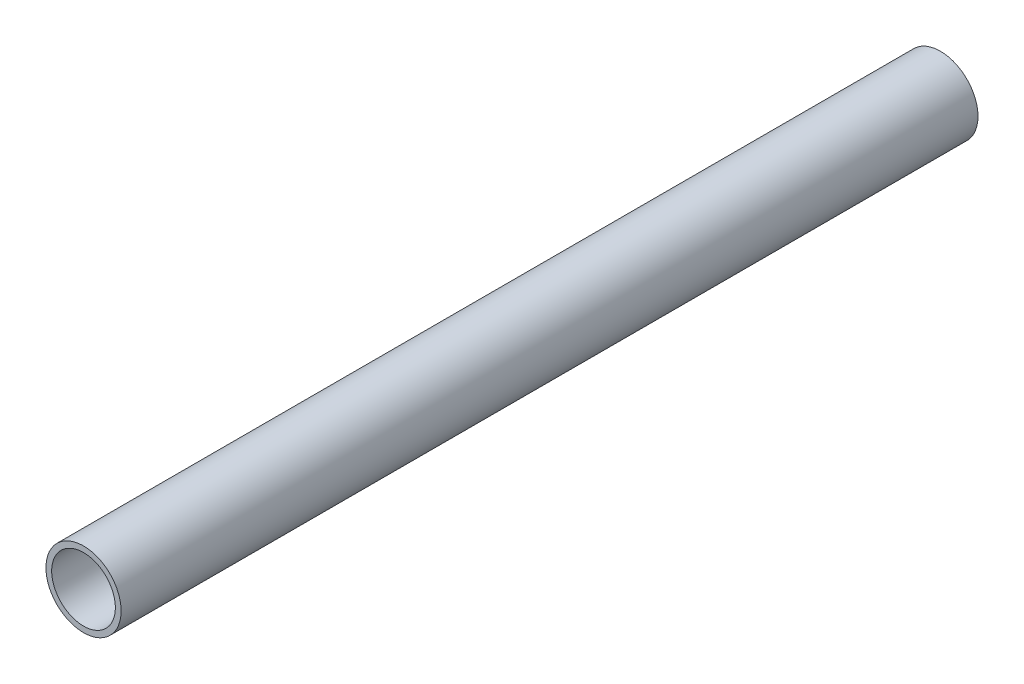
SolidWorks part; units mm, degrees
material "Alloy Steel"
ref_plane "Front Plane" through (0, 0, 0) normal (0, 0, 1) x (1, 0, 0)
ref_plane "Top Plane" through (0, 0, 0) normal (0, 1, 0) x (1, 0, 0)
ref_plane "Right Plane" through (0, 0, 0) normal (1, 0, 0) x (0, 0, -1)
sketch "Croquis1" plane through (0, 0, 0) normal (0, 0, 1) x (1, 0, 0)
  circle A0 centre (0, 0) radius 20.447
  circle A1 centre (0, 0) radius 24.13
  dimension "D1" = 40.894
  dimension "D2" = 48.26
extrude "Saliente-Extruir1" add sketch "Croquis1" against normal blind 550
equation "\"IDcase\"=40.894"
equation "\"D1@Croquis1\"=\"IDcase\""
equation "\"ODcase\"=48.26"
equation "\"D2@Croquis1\"=\"ODcase\""
